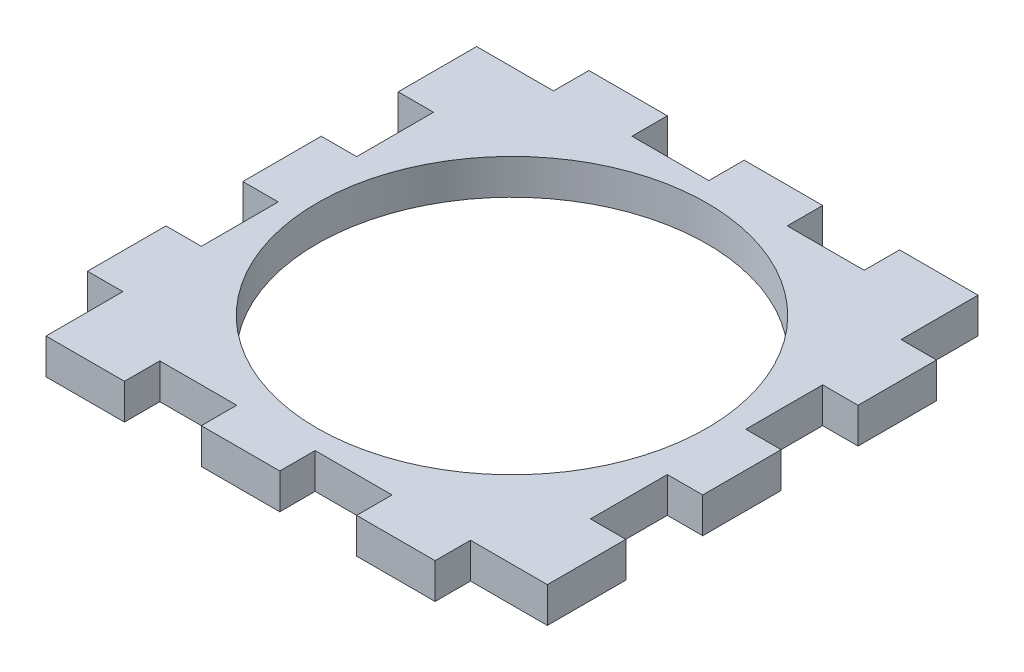
SolidWorks part; units mm, degrees
material "Acrylic (Medium-high impact)"
ref_plane "Front Plane" through (0, 0, 0) normal (0, 0, 1) x (1, 0, 0)
ref_plane "Top Plane" through (0, 0, 0) normal (0, 1, 0) x (1, 0, 0)
ref_plane "Right Plane" through (0, 0, 0) normal (1, 0, 0) x (0, 0, -1)
sketch "Sketch2" plane through (0, 0, 0) normal (0, 1, 0) x (1, 0, 0)
  line L1 (-19.325, 19.325) -> (19.325, 19.325)
  line L2 (-19.325, 19.325) -> (-19.325, -19.325)
  line L3 (-19.325, -19.325) -> (19.325, -19.325)
  line L4 (19.325, 19.325) -> (19.325, -19.325)
  line L5 (-19.325, 19.325) -> (19.325, -19.325) construction
  line L6 (-19.325, -19.325) -> (19.325, 19.325) construction
  point P0 (0, 0)
  dimension "D2" = 38.65
  dimension "D1" = 38.65
extrude "Boss-Extrude1" add sketch "Sketch2" along normal mid plane 3.175
sketch "Sketch4" plane through (0, 0, -19.325) normal (0, 0, -1) x (-1, 0, 0)
  line L0 (-19.325, -1.5875) -> (19.325, -1.5875) construction
  line L1 (19.325, 1.5875) -> (11.9309, 1.5875)
  line L2 (19.325, 1.5875) -> (19.325, -1.5875)
  line L3 (19.325, -1.5875) -> (11.9309, -1.5875)
  line L4 (11.9309, 1.5875) -> (11.9309, -1.5875)
  dimension "D1" = 7.3941
extrude "Boss-Extrude2" [suppressed] add sketch "Sketch4" along normal blind 3.175
sketch "Sketch5" plane through (0, 0, 19.325) normal (0, 0, 1) x (1, 0, 0)
  line L0 (-19.325, 1.5875) -> (19.325, 1.5875) construction
  line L1 (-19.255, -1.5875) -> (-12.825, -1.5875)
  line L2 (-19.255, -1.5875) -> (-19.255, 1.5875)
  line L3 (-19.255, 1.5875) -> (-12.825, 1.5875)
  line L4 (-12.825, -1.5875) -> (-12.825, 1.5875)
  line L5 (-19.325, 1.5875) -> (-19.325, -1.5875) construction
  line L6 (-19.325, -1.5875) -> (19.325, -1.5875) construction
  dimension "D2" = 0.07
  dimension "D1" = 6.43
extrude "Cut-Extrude2" [suppressed] cut sketch "Sketch5" against normal blind 3.175
pattern_linear "LPattern1" [suppressed] count 3 spacing 13.9417 of bodies 104
pattern_linear "LPattern2" [suppressed] count 3 spacing 13.9417 of bodies 105
sketch "Sketch7" [suppressed] plane through (-20.9125, 0, 0) normal (-1, 0, 0) x (0, 0, 1)
  line L0 (-24.09, 1.5875) -> (20.915, 1.5875) construction
  line L1 (-20.915, 1.5875) -> (-14.0142, 1.5875)
  line L2 (-20.915, 1.5875) -> (-20.915, -1.5875)
  line L3 (-20.915, -1.5875) -> (-14.0142, -1.5875)
  line L4 (-14.0142, 1.5875) -> (-14.0142, -1.5875)
  line L5 (-24.09, -1.5875) -> (20.915, -1.5875) construction
  line L6 (-24.09, -1.5875) -> (-24.09, 1.5875) construction
  dimension "D1" = 3.175
  dimension "D2" = 10.4104
extrude "Cut-Extrude3" [suppressed] cut sketch "Sketch7" against normal blind 3.175
sketch "Sketch8" plane through (-19.325, 0, 0) normal (-1, 0, 0) x (0, 0, 1)
  line L0 (-19.325, 1.5875) -> (19.325, 1.5875) construction
  line L1 (-19.325, -1.5875) -> (-12.2842, -1.5875)
  line L2 (-19.325, -1.5875) -> (-19.325, 1.5875)
  line L3 (-19.325, 1.5875) -> (-12.2842, 1.5875)
  line L4 (-12.2842, -1.5875) -> (-12.2842, 1.5875)
  dimension "D1" = 7.0408
extrude "Boss-Extrude3" add sketch "Sketch8" along normal blind 3.175
pattern_linear "LPattern3" count 3 spacing 13.9417 along (0, 0, 1) of "Boss-Extrude3"
ref_axis "Axis1" through (0, 0, 0) along (0, 1, 0)
pattern_circular "CirPattern1" count 4 every 90 about axis through (0, 0, 0) along (0, 1, 0) of "Boss-Extrude3", "LPattern3"
sketch "Sketch9" [suppressed] plane through (-20.9125, 0, 0) normal (-1, 0, 0) x (0, 0, 1)
  line L0 (-24.09, -1.5875) -> (20.915, -1.5875) construction
  line L1 (17.67, 1.5875) -> (10.7692, 1.5875)
  line L2 (17.67, 1.5875) -> (17.67, -1.5875)
  line L3 (17.67, -1.5875) -> (10.7692, -1.5875)
  line L4 (10.7692, 1.5875) -> (10.7692, -1.5875)
  line L7 (-24.09, 1.5875) -> (20.915, 1.5875) construction
  line L8 (20.915, 1.5875) -> (20.915, -1.5875) construction
  dimension "D1" = 7.9171
  dimension "D2" = 3.245
sketch "Sketch10" [suppressed] plane through (0, 0, 20.915) normal (0, 0, 1) x (1, 0, 0)
  line L1 (-20.9125, 1.5875) -> (-20.8425, 1.5875)
  line L2 (-20.9125, 1.5875) -> (-20.9125, -1.5875)
  line L3 (-20.9125, -1.5875) -> (-20.8425, -1.5875)
  line L4 (-20.8425, 1.5875) -> (-20.8425, -1.5875)
extrude "Cut-Extrude5" [suppressed] cut sketch "Sketch10" against normal blind 3.175
extrude "Cut-Extrude4" [suppressed] cut sketch "Sketch9" against normal blind 3.175
sketch "Sketch11" [suppressed] plane through (-20.9125, 0, 0) normal (-1, 0, 0) x (0, 0, 1)
  line L1 (17.67, 1.5875) -> (17.74, 1.5875)
  line L2 (17.67, 1.5875) -> (17.67, -1.5875)
  line L3 (17.67, -1.5875) -> (17.74, -1.5875)
  line L4 (17.74, 1.5875) -> (17.74, -1.5875)
extrude "Cut-Extrude6" [suppressed] cut sketch "Sketch11" against normal blind 3.175
pattern_linear "LPattern4" [suppressed] count 3 spacing 13.9417 of bodies 114
sketch "Sketch14" plane through (19.325, 0, 0) normal (1, 0, 0) x (0, 0, -1)
  line L0 (-19.325, 1.5875) -> (19.325, 1.5875) construction
  line L1 (-16.15, 1.5875) -> (-9.3991, 1.5875)
  line L2 (-16.15, 1.5875) -> (-16.15, -1.5875)
  line L3 (-16.15, -1.5875) -> (-9.3991, -1.5875)
  line L4 (-9.3991, 1.5875) -> (-9.3991, -1.5875)
  line L5 (-19.325, -1.5875) -> (19.325, -1.5875) construction
  line L7 (-19.325, 1.5875) -> (-19.325, -1.5875) construction
  dimension "D2" = 6.7509
  dimension "D1" = 3.175
extrude "Cut-Extrude7" [suppressed] cut sketch "Sketch14" against normal blind 3.175
pattern_linear "LPattern5" [suppressed] count 3 spacing 13.9417 of bodies 118
sketch "Sketch15" plane through (0, 1.5875, 0) normal (0, 1, 0) x (1, 0, 0)
  circle A0 centre (0, 0) radius 17.5
  dimension "D1" = 35
extrude "Cut-Extrude8" cut sketch "Sketch15" against normal through all
equation "\"width\"= 3.175mm"
equation "\"kerf\"= 0.07mm"
equation "\"D1@Sketch4\"       = 6.5+\"kerf\""
equation "\"D2@Sketch7\"        = 6.5-\"kerf\""
equation "\"D1@Sketch8\" = \"length\" / ( \"tabs\" * 2 ) + \"kerf\""
equation "\"D1@Sketch9\"        = 6.5-\"kerf\""
equation "\"D2@Sketch9\"=\"width\"+\"kerf\""
equation "\"D2@Sketch14\"        = 6.5-\"kerf\""
equation "\"D1@Sketch14\"=\"width\"+\"kerf\""
equation "\"D1@Sketch5\"        = 4.5-\"kerf\""
equation "\"length\"= 45 - \"width\""
equation "\"D3@LPattern1\" = \"length\" / \"tabs\""
equation "\"D3@LPattern2\" = \"length\" / \"tabs\""
equation "\"D3@LPattern4\" = \"length\" / \"tabs\""
equation "\"D3@LPattern5\" = \"length\" / \"tabs\""
equation "\"D3@LPattern3\" = \"length\" / \"tabs\""
equation "\"tabs\"= 3"
equation "\"D1@LPattern1\"=\"tabs\""
equation "\"D1@LPattern2\"=\"tabs\""
equation "\"D1@LPattern4\"=\"tabs\""
equation "\"D1@LPattern5\"=\"tabs\""
equation "\"D1@LPattern3\"=\"tabs\""
equation "\"D2@Sketch2\"=\"length\"-\"width\""
equation "\"D1@Sketch2\"=\"length\"-\"width\""
equation "\"D2@Sketch3\"=6.5+\"kerf\""
